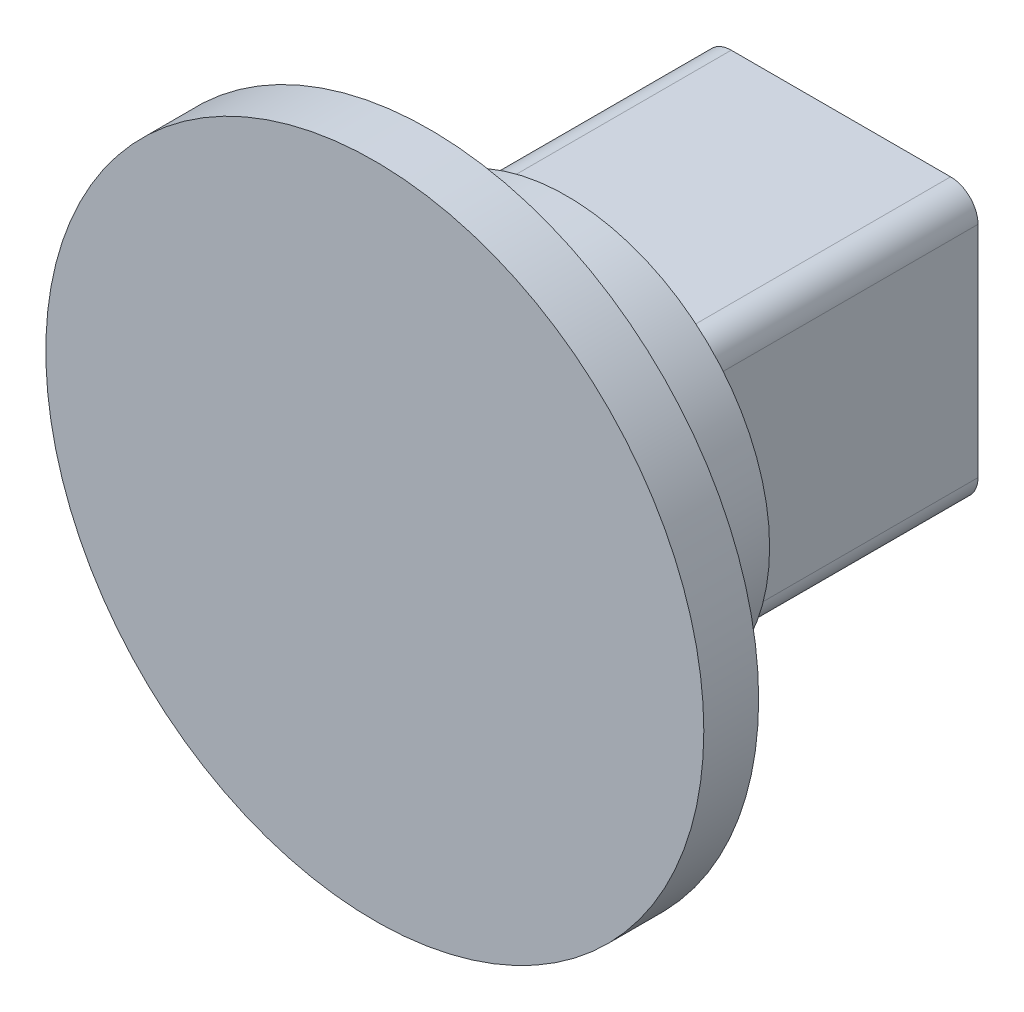
SolidWorks part; units mm, degrees
ref_plane "Front Plane" through (0, 0, 0) normal (0, 0, 1) x (1, 0, 0)
ref_plane "Top Plane" through (0, 0, 0) normal (0, 1, 0) x (1, 0, 0)
ref_plane "Right Plane" through (0, 0, 0) normal (1, 0, 0) x (0, 0, -1)
sketch "Sketch1" plane through (0, 0, 0) normal (0, 0, 1) x (1, 0, 0)
  line L1 (-5, -5) -> (5, -5)
  line L2 (-5, -5) -> (-5, 5)
  line L3 (-5, 5) -> (5, 5)
  line L4 (5, -5) -> (5, 5)
  line L5 (-5, -5) -> (5, 5) construction
  line L6 (-5, 5) -> (5, -5) construction
  circle A0 centre (0, 0) radius 7.4
  dimension "D1" = 14.8
  dimension "D3" = 10
  dimension "D4" = 10
extrude "Boss-Extrude1" add sketch "Sketch1" against normal blind 10 contours L4 L3 L2 L1
extrude "Boss-Extrude2" add sketch "Sketch1<4>" along normal blind 5 contours A0
sketch "Sketch1<4>" plane through (0, 0, 0) normal (0, 0, 1) x (1, 0, 0) same geometry as "Sketch1"
fillet "Fillet1" radius 1 4 edges at (5, 5, -5) (-5, 5, -5) (-5, -5, -5) (5, -5, -5)
sketch "Sketch2" plane through (0, 0, 0) normal (0, 0, 1) x (1, 0, 0)
  circle A0 centre (0, 0) radius 12
  dimension "D1" = 24
extrude "Boss-Extrude3" add sketch "Sketch2" along normal blind 2 from surface starting at face at (7.4, 0, 5)
sketch "Sketch3" plane through (0, 0, 0) normal (0, 0, 1) x (1, 0, 0)
  line L0 (0, 0) -> (0, 16.1137) construction
  line L1 (0, 0) -> (0, -19.6849) construction
  line L2 (0, 0) -> (-9.7508, 13.9256) construction
  line L3 (0, 0) -> (-15.2488, -18.1728) construction
  line L4 (0, 0) -> (-26.1304, 0) construction
  line L5 (-3.1547, 4.5053) -> (5.5819, 10.6227)
  line L6 (-3.5353, -4.2132) -> (4.6348, -11.0688)
  circle A0 centre (0, 0) radius 8.5 construction
  circle A1 centre (-4.8754, 6.9628) radius 3
  circle A2 centre (-5.4637, -6.5114) radius 3
  circle A3 centre (-8.5, 0) radius 1.5
  circle A4 centre (0, 0) radius 5.5
  circle A6 centre (0, 0) radius 12
  dimension "D3" = 6
  dimension "D4" = 6
  dimension "D5" = 17
  dimension "D6" = 3
  dimension "D7" = 24
  dimension "D1" = 55
  dimension "D2" = 50
